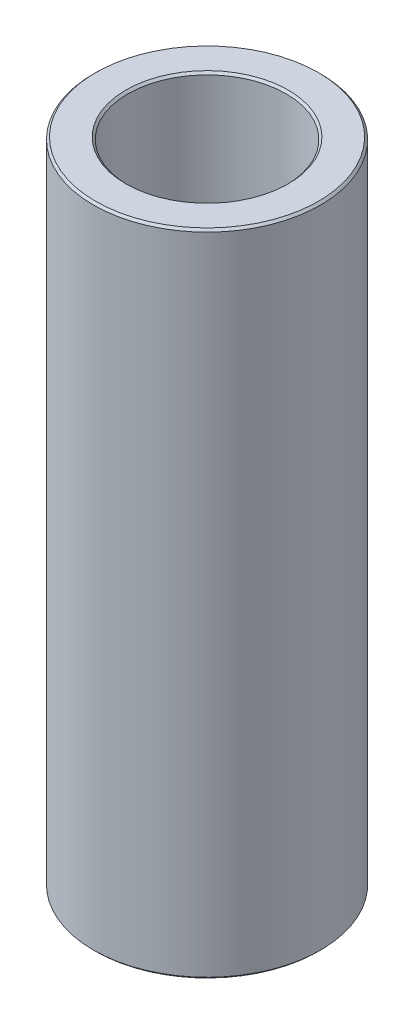
SolidWorks part; units mm, degrees
ref_plane "Front Plane" through (0, 0, 0) normal (0, 0, 1) x (1, 0, 0)
ref_plane "Top Plane" through (0, 0, 0) normal (0, 1, 0) x (1, 0, 0)
ref_plane "Right Plane" through (0, 0, 0) normal (1, 0, 0) x (0, 0, -1)
sketch "Sketch1" plane through (0, 0, 0) normal (0, 1, 0) x (1, 0, 0)
  circle A0 centre (0, 0) radius 35
  dimension "SLEEVE_OD" = 70
extrude "Boss-Extrude1" add sketch "Sketch1" along normal blind 200.1673
sketch "Sketch2" plane through (0, 0, 0) normal (0, 1, 0) x (1, 0, 0)
  circle A0 centre (0, 0) radius 24.3753
  dimension "BORE_D" = 48.7506
extrude "Cut-Extrude1" cut sketch "Sketch2" along normal through all
chamfer "Chamfer1" distance 0.6637 angle 45 4 edges at (0, 200.1673, 24.3753) (0, 0, 24.3753) (0, 0, 35) (0, 200.1673, 35)
